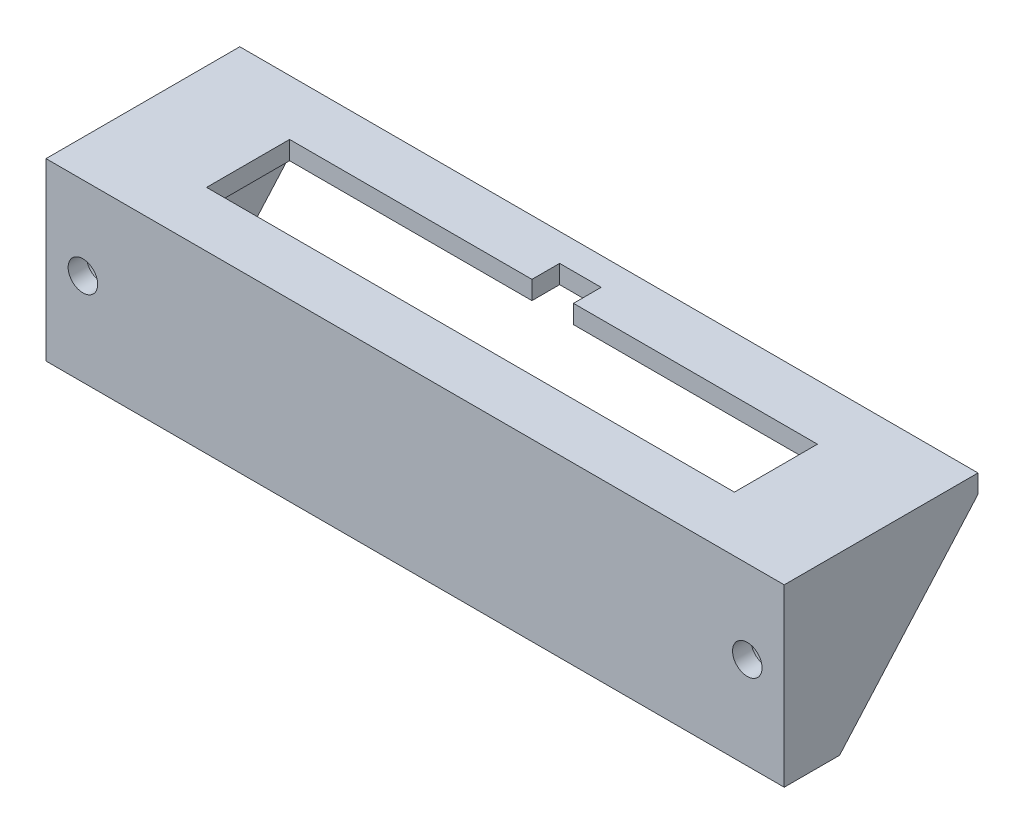
SolidWorks part; units mm, degrees
ref_plane "Front Plane" through (0, 0, 0) normal (0, 0, 1) x (1, 0, 0)
ref_plane "Top Plane" through (0, 0, 0) normal (0, 1, 0) x (1, 0, 0)
ref_plane "Right Plane" through (0, 0, 0) normal (1, 0, 0) x (0, 0, -1)
ref_plane "Plane1" through (0, 12.25, 0) normal (0, 1, 0) x (1, 0, 0)
sketch "Sketch1" plane through (0, 12.25, 0) normal (0, 1, 0) x (1, 0, 0)
  line L1 (-23.0811, -28.0873) -> (34.1189, -28.0873)
  line L2 (-23.0811, -28.0873) -> (-23.0811, -19.0873)
  line L3 (-23.0811, -19.0873) -> (3.1811, -19.0873)
  line L4 (34.1189, -28.0873) -> (34.1189, -19.0873)
  line L9 (7.6811, -19.0873) -> (34.1189, -19.0873)
  line L11 (3.1811, -19.0873) -> (3.1811, -16.0873)
  line L12 (3.1811, -16.0873) -> (7.6811, -16.0873)
  line L13 (7.6811, -19.0873) -> (7.6811, -16.0873)
  line L23 (-34.4811, -13.0873) -> (45.5189, -13.0873)
  line L24 (-34.4811, -13.0873) -> (-34.4811, -34.0873)
  line L25 (-34.4811, -34.0873) -> (45.5189, -34.0873)
  line L26 (45.5189, -13.0873) -> (45.5189, -34.0873)
  dimension "D1" = 57.2
  dimension "D2" = 9
  dimension "D4" = 4.5
  dimension "D5" = 3
  dimension "D6" = 0.5
  dimension "D7" = 0.5
  dimension "D8" = 6
  dimension "D3" = 6
  dimension "D9" = 80
  dimension "D10" = 11.4
  dimension "D11" = 11.4
extrude "Boss-Extrude1" add sketch "Sketch1" along normal blind 2
ref_plane "Plane2" through (5.5189, 0, 0) normal (-1, 0, 0) x (0, 0, 1)
sketch "Sketch2" plane through (-34.4811, 0, 0) normal (-1, 0, 0) x (0, 0, 1)
  line L6 (34.0873, 12.25) -> (34.0873, -4.75)
  line L7 (34.0873, -4.75) -> (28.0873, -4.75)
  line L8 (28.0873, -4.75) -> (13.0873, 12.25)
  line L9 (13.0873, 12.25) -> (34.0873, 12.25)
  point P5 (31.0873, -4.75)
  dimension "D1" = 17
  dimension "D2" = 6
extrude "Boss-Extrude2" add sketch "Sketch2" against normal blind 8 contours L7 L8 L9 L6
sketch "Sketch3" plane through (0, 0, 0) normal (0, 0, 1) x (1, 0, 0)
  line L1 (-26.4811, -4.75) -> (-34.4811, -4.75) construction
  line L3 (-26.4811, -4.75) -> (-34.4811, -4.75) construction
  circle A0 centre (-30.4811, 5.25) radius 1.6
  circle A1 centre (-30.4811, 5.25) radius 3.1
  point P2 (-30.4811, -4.75)
  dimension "D1" = 3.2
  dimension "D2" = 10
  dimension "D3" = 1.5
extrude "Cut-Extrude1" cut sketch "Sketch3" against normal through all both and the other way through all contours A0
extrude "Cut-Extrude2" cut sketch "Sketch3<5>" along normal offset from surface (32.0873 mm away) 2 contours A1 | A0 up to face at (-28.8811, 5.25, 34.0873)
sketch "Sketch3<5>" plane through (0, 0, 0) normal (0, 0, 1) x (1, 0, 0) same geometry as "Sketch3"
mirror "Mirror1" about plane through (5.5189, 0, 0) normal (-1, 0, 0) of "Cut-Extrude2", "Cut-Extrude1", "Boss-Extrude2"
sketch "Sketch4" plane through (0, 12.25, 0) normal (0, -1, 0) x (1, 0, 0)
  line L0 (37.5189, 28.0873) -> (37.5189, 13.0873) construction
  line L1 (-26.4811, 34.0873) -> (37.5189, 34.0873)
  line L2 (-26.4811, 34.0873) -> (-26.4811, 28.0873)
  line L3 (-26.4811, 28.0873) -> (37.5189, 28.0873)
  line L4 (37.5189, 34.0873) -> (37.5189, 28.0873)
  point P7 (37.5189, 28.0873)
extrude "Boss-Extrude5" add sketch "Sketch4" along normal up to surface (17 mm away) contours L2 L1 L4 L3 up to face at (-30.4811, -4.75, 31.0873)
